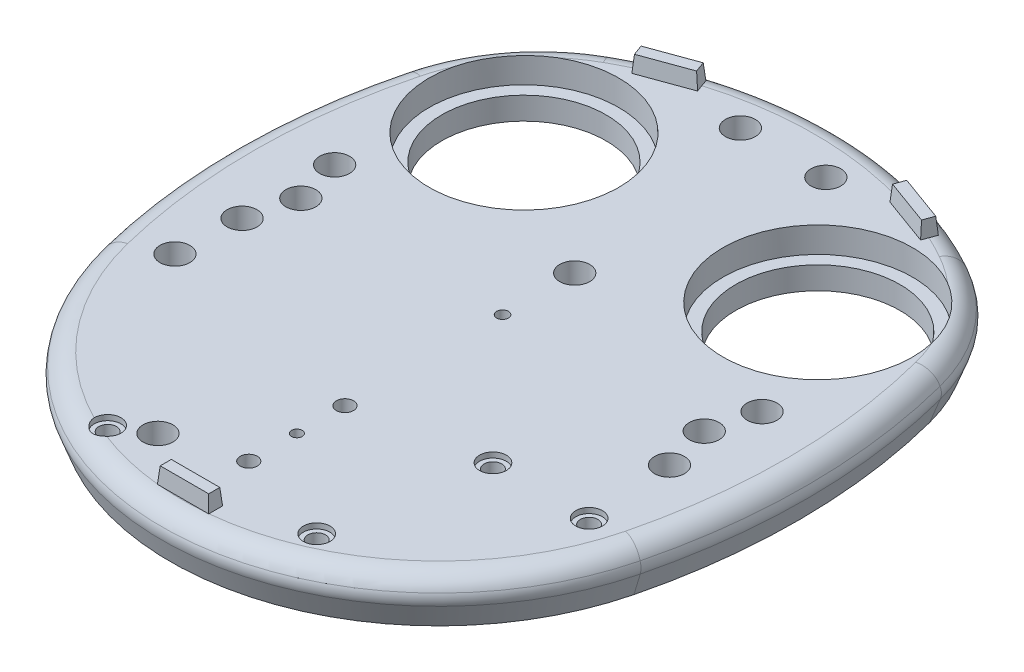
SolidWorks part; units mm, degrees
ref_plane "Front" through (0, 0, 0) normal (0, 0, 1) x (1, 0, 0)
ref_plane "Top" through (0, 0, 0) normal (0, 1, 0) x (1, 0, 0)
ref_plane "Right" through (0, 0, 0) normal (1, 0, 0) x (0, 0, -1)
sketch "Knuckle Spacing" plane through (0, 0, 0) normal (0, 1, 0) x (1, 0, 0)
  line L0 (-27.5, 0) -> (27.5, 0) construction
  line L1 (0, 0) -> (0, -70) construction
  circle A0 centre (-27.5, 0) radius 15 construction
  circle A1 centre (27.5, 0) radius 15 construction
  circle A2 centre (0, -70) radius 15 construction
  dimension "D3" = 30
  dimension "D1" = 55
  dimension "D2" = 70
sketch "XL320" plane through (0, 0, 0) normal (0, 1, 0) x (1, 0, 0)
  line L0 (-0.4, -12) -> (-36.4, 12) construction
  line L1 (-36.4, -12) -> (-0.4, 12) construction
  line L2 (-0.4, 12) -> (-0.4, -12)
  line L3 (-0.4, -12) -> (-36.4, -12)
  line L4 (-36.4, 12) -> (-36.4, -12)
  line L5 (-36.4, 12) -> (-0.4, 12)
  line L6 (-27.5, 0) -> (27.5, 0) construction
  line L7 (0.4, 12) -> (36.4, -12) construction
  line L8 (36.4, -12) -> (36.4, 12)
  line L9 (36.4, 12) -> (0.4, 12)
  line L10 (0.4, -12) -> (36.4, 12) construction
  line L11 (36.4, -12) -> (0.4, -12)
  line L12 (0.4, 12) -> (0.4, -12)
  circle A0 centre (-27.5, 0) radius 8.9
  circle A1 centre (27.5, 0) radius 8.9
  point P10 (-18.4, 0)
  point P17 (18.4, 0)
  dimension "D1" = 17.8
  dimension "D4" = 17.8
  dimension "D2" = 36
  dimension "D3" = 24
  dimension "D5" = 36
  dimension "D6" = 24
sketch "Sketch1" plane through (0, 0, 0) normal (0, 1, 0) x (1, 0, 0)
  line L0 (0, 0) -> (0, -70) construction
  circle A0 centre (-27.5, 0) radius 17.75
  circle A1 centre (27.5, 0) radius 17.75
  circle A2 centre (27.5, 0) radius 20
  circle A3 centre (-27.5, 0) radius 20
  arc A4 (48.5499, -55.5542) -> (46.555, 6.0751) centre (-61.1312, -28.2576) ccw
  arc A5 (-39.2984, 16.1492) -> (39.2984, 16.1492) centre (0, -37.641) cw
  arc A6 (-48.5499, -55.5542) -> (-46.555, 6.0751) centre (61.1312, -28.2576) cw
  arc A7 (48.5499, -55.5542) -> (-48.5499, -55.5542) centre (0, -43.4715) cw
  dimension "D1" = 35.5
  dimension "D2" = 40
  dimension "D3" = 66.6164
  dimension "D5" = 113.0268
  dimension "D6" = 113.0268
  dimension "D7" = 50.0309
  dimension "D4" = 122.2625
extrude "Boss-Extrude1" add sketch "Sketch1" along normal blind 9 contours A7 A4 A2 A5 A3 A6 | A3 A0 | A2 A1 region at (10.1723, 0, 8.8001) region at (0, 0, 40.7131) region at (-18.6999, 0, -17.3277)
sketch "Sketch2" plane through (0, 0, 0) normal (0, 1, 0) x (1, 0, 0)
  circle A0 centre (-27.5, 0) radius 15.375
  circle A1 centre (27.5, 0) radius 15.375
  circle A2 centre (-27.5, 0) radius 17.75
  circle A3 centre (27.5, 0) radius 17.75
  dimension "D1" = 30.75
  dimension "D2" = 35.5
extrude "Boss-Extrude3" add sketch "Sketch2" along normal blind 4.215
sketch "Sketch3" plane through (0, 9, 0) normal (0, 1, 0) x (1, 0, 0)
  circle A0 centre (-27.5, 0) radius 17.75
  circle A1 centre (27.5, 0) radius 17.75
  dimension "D1" = 35.5
sketch "Sketch4" plane through (0, 9, 0) normal (0, 1, 0) x (1, 0, 0)
  line L0 (0, 0) -> (0, -70) construction
  line L1 (0, 0) -> (0, -70) construction
  line L2 (-27.5, 0) -> (27.5, 0) construction
  circle A0 centre (-8, 21.01) radius 2.8
  circle A2 centre (0, -18) radius 2.8
  circle A3 centre (-40, -22.9303) radius 2.8
  circle A4 centre (-37.75, -31.5038) radius 2.8
  circle A5 centre (-40, -40.255) radius 2.8
  circle A6 centre (-40.5, -52.3285) radius 2.8
  circle A7 centre (-13, -83) radius 2.8
  circle A9 centre (40, -40.255) radius 2.8
  circle A10 centre (37.75, -31.5038) radius 2.8
  circle A11 centre (40, -22.9303) radius 2.8
  circle A12 centre (8, 21.01) radius 2.8
  dimension "D1" = 5.6
  dimension "D3" = 21.01
  dimension "D2" = 19.5
  dimension "D4" = 18
  dimension "D5" = 22.9303
  dimension "D6" = 40
  dimension "D7" = 37.75
  dimension "D8" = 40.255
  dimension "D9" = 40
  dimension "D10" = 8.5735
  dimension "D11" = 12.0735
  dimension "D12" = 40.5
  dimension "D13" = 13
  dimension "D14" = 13
extrude "M3_Tapping_Insert_Holes" cut sketch "Sketch4" against normal blind 7
sketch "Sketch5" plane through (0, 9, 0) normal (0, 1, 0) x (1, 0, 0)
  line L0 (0, 0) -> (0, -70) construction
  line L1 (0, 0) -> (0, -8.2743) construction
  line L2 (0, -8.2743) -> (-16.3604, -8.2743) construction
  line L3 (0, -8.2743) -> (16.3604, -8.2743) construction
  arc A0 (-50.2517, 0.4655) -> (-33.3942, 22.301) centre (-16.3604, -8.2743) cw
  arc A1 (50.2517, 0.4655) -> (33.3942, 22.301) centre (16.3604, -8.2743) ccw
  arc A2 (-33.3942, 22.301) -> (33.3942, 22.301) centre (0, -37.641) cw
  arc A3 (-50.2517, 0.4655) -> (-50.4907, -56.0372) centre (61.1312, -28.2576) ccw
  arc A4 (50.2517, 0.4655) -> (50.4907, -56.0372) centre (-61.1312, -28.2576) cw
  arc A6 (-50.4907, -56.0372) -> (50.4907, -56.0372) centre (0, -43.4715) ccw
  arc A7 (48.5499, -55.5542) -> (46.555, 6.0751) centre (-61.1312, -28.2576) ccw
  arc A11 (-48.5499, -55.5542) -> (48.5499, -55.5542) centre (0, -43.4715) ccw construction
  arc A12 (39.2984, 16.1492) -> (-39.2984, 16.1492) centre (0, -37.641) ccw construction
  arc A15 (-46.555, 6.0751) -> (-48.5499, -55.5542) centre (61.1312, -28.2576) ccw
  arc A16 (-46.555, 6.0751) -> (-48.5499, -55.5542) centre (61.1312, -28.2576) ccw construction
  arc A17 (-48.5499, -55.5542) -> (48.5499, -55.5542) centre (0, -43.4715) ccw
  arc A18 (-39.2984, 16.1492) -> (39.2984, 16.1492) centre (0, -37.641) cw
  circle A19 centre (27.5, 0) radius 20 construction
  arc A20 (39.2984, 16.1492) -> (46.555, 6.0751) centre (27.5, 0) cw
  arc A21 (-46.555, 6.0751) -> (-39.2984, 16.1492) centre (-27.5, 0) cw
  point P17 (0, -93.5023)
  point P18 (0, -95.5023)
  point P22 (0, 30.9755)
  point P23 (0, 28.9755)
  dimension "D1" = 35
  dimension "D2" = 35
  dimension "D4" = 2
  dimension "D5" = 52.0309
  dimension "D6" = 16.3604
  dimension "D8" = 115.0268
  dimension "D9" = 115.0268
  dimension "D10" = 8.2743
extrude "Extrude-Thin2" add sketch "Sketch5" against normal blind 9 thin contours A20 A18 A21 A15 A17 A7 | A4 A6 A3 A0 A2 A1 thin type one direction reverse wall 2
sketch "Sketch7" plane through (0, 9, 0) normal (0, 1, 0) x (1, 0, 0)
  circle A0 centre (0, -70) radius 15.25
  dimension "D1" = 30.5
extrude "Thumb_Knuckle_Hole" cut sketch "Sketch7" against normal through all from offset 4.5875 offset against normal yes
sketch "Sketch8" plane through (0, 9, 0) normal (0, 1, 0) x (1, 0, 0)
  line L0 (0, 0) -> (0, -70) construction
  circle A0 centre (0, -70) radius 1
  circle A1 centre (0, -61) radius 1.6
  circle A2 centre (0, -79) radius 1.6
  dimension "D1" = 3.2
  dimension "D3" = 2
  dimension "D4" = 3.2
  dimension "D2" = 9
  dimension "D5" = 9
extrude "Thumb_Through_Hole(s)" cut sketch "Sketch8" against normal through all
sketch "Sketch9" plane through (0, 9, 0) normal (0, 1, 0) x (1, 0, 0)
  line L0 (0, -18) -> (0, -31.5038) construction
  line L1 (0, 0) -> (0, -70) construction
  circle A0 centre (0, -31.5038) radius 1.1
  dimension "D1" = 2.2
  dimension "D2" = 13.5038
extrude "Center_Screw_Through" cut sketch "Sketch9" against normal through all
chamfer "Chamfer1" distance 5 angle 20.5 6 edges at (44.0649, 0, -13.1141) (0, 0, -30.9755) (53.8945, 0, 27.771) (-44.0649, 0, -13.1141) (0, 0, 95.5023) (-53.8945, 0, 27.771) first distance on face at (42.9439, 4.5, -12.2487) first distance on face at (0, 4.5, -26.6382) first distance on face at (52.1329, 4.5, 27.7784) first distance on face at (-42.9439, 4.5, -12.2487) first distance on face at (0, 4.5, 75.7698) first distance on face at (-52.1329, 4.5, 27.7784)
fillet "Fillet1" radius 4 6 edges at (-44.0649, 9, -13.1141) (0, 9, -30.9755) (44.0649, 9, -13.1141) (53.8945, 9, 27.771) (0, 9, 95.5023) (-53.8945, 9, 27.771)
fillet "Fillet2" radius 3 6 edges at (44.0649, 5, -13.1141) (53.8945, 5, 27.771) (0, 5, 95.5023) (-53.8945, 5, 27.771) (-44.0649, 5, -13.1141) (0, 5, -30.9755)
sketch "Sketch10" plane through (0, 9, 0) normal (0, 1, 0) x (1, 0, 0)
  line L0 (-18.8893, 25.4432) -> (-18, 23)
  line L1 (-4.8, -91.3) -> (4.8, -91.3)
  line L2 (-4.8, -91.3) -> (-4.8, -88.7)
  line L3 (-4.8, -88.7) -> (4.8, -88.7)
  line L4 (4.8, -91.3) -> (4.8, -88.7)
  line L5 (-4.8, -91.3) -> (4.8, -88.7) construction
  line L6 (-4.8, -88.7) -> (4.8, -91.3) construction
  line L7 (-18, 23) -> (-27.021, 19.7166)
  line L8 (-27.021, 19.7166) -> (-27.9103, 22.1598)
  line L9 (-27.9103, 22.1598) -> (-18.8893, 25.4432)
  line L10 (18.8893, 25.4432) -> (18, 23)
  line L11 (18, 23) -> (27.021, 19.7166)
  line L12 (27.021, 19.7166) -> (27.9103, 22.1598)
  line L13 (27.9103, 22.1598) -> (18.8893, 25.4432)
  line L14 (0, 0) -> (0, 50) construction
  line L15 (-27.5, 0) -> (27.5, 0) construction
  line L16 (0, 0) -> (0, -70) construction
  point P0 (0, -90)
  dimension "D1" = 50
  dimension "D2" = 23
  dimension "D3" = 18
  dimension "D4" = 20
  dimension "D5" = 9.6
  dimension "D6" = 2.6
  dimension "D7" = 90
  dimension "D8" = 9.6
  dimension "D9" = 2.6
extrude "Chamfer_Fits" add sketch "Sketch10" along normal blind 3 draft 5
sketch "Sketch11" plane through (0, 9, 0) normal (0, 1, 0) x (1, 0, 0)
  circle A0 centre (23.1124, -56.412) radius 1.65
  circle A1 centre (41.1124, -56.412) radius 1.65
  circle A2 centre (18.1124, -84.412) radius 1.65
  circle A3 centre (-19.0056, -86.412) radius 1.65
  dimension "D1" = 3.3
  dimension "D2" = 19.0056
  dimension "D3" = 86.412
  dimension "D4" = 84.412
  dimension "D5" = 18.1124
  dimension "D6" = 23.1124
  dimension "D7" = 56.412
  dimension "D8" = 56.412
  dimension "D9" = 41.1124
extrude "M2_Press_Insert_Holes" cut sketch "Sketch11" against normal blind 5
sketch "Sketch12" plane through (0, 9, 0) normal (0, 1, 0) x (1, 0, 0)
  circle A0 centre (23.1124, -56.412) radius 2.5
  circle A1 centre (41.1124, -56.412) radius 2.5
  circle A2 centre (18.1124, -84.412) radius 2.5
  circle A3 centre (-19.0056, -86.412) radius 2.5
  dimension "D1" = 5
extrude "M2_Press_Insert_Head" cut sketch "Sketch12" against normal blind 1
